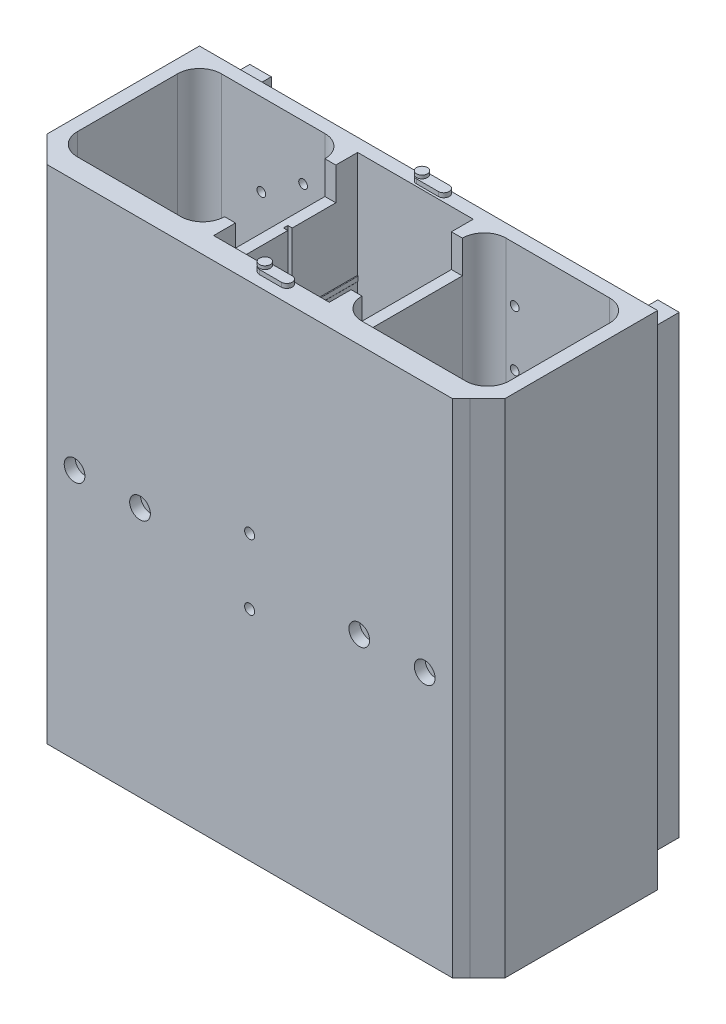
SolidWorks part; units mm, degrees
ref_plane "前视基准面" through (0, 0, 0) normal (0, 0, 1) x (1, 0, 0)
ref_plane "上视基准面" through (0, 0, 0) normal (0, 1, 0) x (1, 0, 0)
ref_plane "右视基准面" through (0, 0, 0) normal (1, 0, 0) x (0, 0, -1)
other "Configuration Table"
sketch "草图1" plane through (0, 0, 0) normal (0, 0, 1) x (1, 0, 0)
  line L1 (0, 0) -> (210, 0)
  line L2 (0, 0) -> (0, 230)
  line L3 (0, 230) -> (210, 230)
  line L4 (210, 0) -> (210, 230)
  line L5 (0, 0) -> (210, 230) construction
  line L6 (0, 230) -> (210, 0) construction
  line L7 (0, 230) -> (26, 230)
  line L8 (0, 230) -> (0, 0)
  line L9 (0, 0) -> (26, 0)
  point P4 (105, 115)
  point P8 (13, 115)
  dimension "D1" = 230
  dimension "D2" = 210
extrude "凸台-拉伸1" add sketch "草图1" along normal blind 6 contours L1 L4 L3 L2
sketch "草图2" plane through (0, 0, 0) normal (0, 0, -1) x (-1, 0, 0)
  line L0 (0, 230) -> (-210, 230) construction
  line L1 (0, 0) -> (-210, 0) construction
  line L2 (-210, 230) -> (-184, 230)
  line L3 (-210, 230) -> (-210, 0)
  line L4 (-210, 0) -> (-184, 0)
  line L5 (-184, 230) -> (-184, 0) construction
  line L6 (-210, 230) -> (-184, 0) construction
  line L7 (-210, 0) -> (-184, 230) construction
  line L9 (0, 230) -> (-20, 230)
  line L10 (0, 230) -> (0, 0)
  line L11 (0, 0) -> (-20, 0)
  line L13 (0, 230) -> (-20, 0) construction
  line L14 (0, 0) -> (-20, 230) construction
  line L15 (-204.925, 219.25) -> (-195.075, 219.25)
  line L16 (-204.925, 219.25) -> (-204.925, 10.75)
  line L17 (-204.925, 10.75) -> (-195.075, 10.75)
  line L18 (-195.075, 219.25) -> (-195.075, 10.75)
  line L19 (-204.925, 219.25) -> (-195.075, 10.75) construction
  line L20 (-204.925, 10.75) -> (-195.075, 219.25) construction
  line L21 (-17.925, 219.25) -> (-8.075, 219.25)
  line L22 (-17.925, 219.25) -> (-17.925, 10.75)
  line L23 (-17.925, 10.75) -> (-8.075, 10.75)
  line L24 (-8.075, 219.25) -> (-8.075, 10.75)
  line L25 (-17.925, 219.25) -> (-8.075, 10.75) construction
  line L26 (-17.925, 10.75) -> (-8.075, 219.25) construction
  point P6 (-197, 115)
  point P18 (-200, 115)
  point P23 (-13, 115)
  dimension "D1" = 26
  dimension "D2" = 20
  dimension "D3" = 208.5
  dimension "D4" = 9.85
  dimension "D5" = 10
  dimension "D6" = 115
  dimension "D7" = 208.5
  dimension "D8" = 115
  dimension "D9" = 13
  dimension "D10" = 9.85
extrude "凸台-拉伸3" add sketch "草图2" along normal blind 15 contours L18 L15 L16 L17 | L24 L21 L22 L23
sketch "草图3" plane through (0, 0, 0) normal (0, 0, -1) x (-1, 0, 0)
  line L0 (0, 0) -> (-210, 0) construction
  line L1 (-210, 230) -> (-184, 230)
  line L2 (-210, 230) -> (-210, 0)
  line L3 (-210, 0) -> (-184, 0)
  line L4 (-184, 230) -> (-184, 0)
  line L5 (-210, 230) -> (-184, 0) construction
  line L6 (-210, 0) -> (-184, 230) construction
  line L7 (-210, 115) -> (119.2636, 115) construction
  line L8 (0, 230) -> (-20, 230)
  line L9 (0, 230) -> (0, 0)
  line L10 (0, 0) -> (-20, 0)
  line L11 (-20, 230) -> (-20, 0)
  line L12 (0, 230) -> (-20, 0) construction
  line L13 (0, 0) -> (-20, 230) construction
  line L14 (-105, 230) -> (-105, 0) construction
  circle A0 centre (-169.6426, 192.25) radius 2
  circle A1 centre (-150.5, 205) radius 2
  circle A2 centre (-150.5, 179.5) radius 2
  circle A3 centre (-150.5, 50.5) radius 2
  circle A4 centre (-150.5, 25) radius 2
  circle A5 centre (-169.6426, 37.75) radius 2
  circle A6 centre (-34.3574, 192.25) radius 2
  circle A7 centre (-53.5, 205) radius 2
  circle A8 centre (-53.5, 179.5) radius 2
  circle A9 centre (-53.5, 50.5) radius 2
  circle A10 centre (-53.5, 25) radius 2
  circle A11 centre (-34.3574, 37.75) radius 2
  point P4 (-197, 115)
  point P12 (-10, 115)
  dimension "D8" = 4
  dimension "D9" = 4
  dimension "D10" = 4
  dimension "D12" = 4
  dimension "D13" = 4
  dimension "D14" = 4
  dimension "D1" = 26
  dimension "D2" = 20
  dimension "D3" = 25.5
  dimension "D4" = 23
  dimension "D5" = 23
  dimension "D6" = 33.5
  dimension "D7" = 33.5
  dimension "D11" = 90
  dimension "D15" = 25.5
  dimension "D16" = 23
  dimension "D17" = 23
  dimension "D18" = 33.5
  dimension "D19" = 33.5
  dimension "D20" = 90
extrude "切除-拉伸1" cut sketch "草图3" against normal blind 10 contours A10 | A11 | A9 | A6 | A8 | A7 | A1 | A2 | A0 | A4 | A3 | A5
chamfer "倒角1" [suppressed] distance 10 angle 45
sketch "草图5" [suppressed] plane through (0, 0, 0) normal (0, 0, -1) x (-1, 0, 0)
  line L0 (-172.5, 115) -> (-135, 115) construction
  line L1 (-10, 230) -> (-200, 230) construction
  line L2 (-210, 10) -> (-210, 220) construction
  line L5 (-210, 220) -> (-210, 0)
  line L8 (-75, 115) -> (-37.5, 115) construction
  line L9 (-210, 0) -> (-184, 220) construction
  line L10 (0, 10) -> (0, 220) construction
  circle A0 centre (-172.5, 115) radius 2.5
  circle A1 centre (-135, 115) radius 2.5
  circle A2 centre (-75, 115) radius 2.5
  circle A3 centre (-37.5, 115) radius 2.5
  point P12 (-197, 110)
  dimension "D3" = 5
  dimension "D4" = 5
  dimension "D8" = 5
  dimension "D9" = 5
  dimension "D1" = 37.5
  dimension "D2" = 115
  dimension "D5" = 75
  dimension "D6" = 26
  dimension "D7" = 37.5
  dimension "D10" = 115
  dimension "D11" = 75
extrude "切除-拉伸2" [suppressed] cut sketch "草图5" against normal blind 10 contours A0 | A1 | A3 | A2
sketch "草图6" plane through (0, 0, 6) normal (0, 0, 1) x (1, 0, 0)
  line L0 (105, 230) -> (105, 0) construction
  line L3 (0, 115) -> (210, 115) construction
  line L6 (86.25, 115) -> (123.75, 115) construction
  line L7 (105, 133.75) -> (105, 96.25) construction
  circle A2 centre (105, 133.75) radius 2.5
  circle A3 centre (105, 96.25) radius 2.5
  point P7 (105, 115)
  point P11 (105, 115)
  dimension "D1" = 37.5
  dimension "D2" = 5
  dimension "D3" = 5
extrude "切除-拉伸3" [suppressed] cut sketch "草图6" against normal blind 10
sketch "草图7" [suppressed] plane through (0, 0, 18) normal (0, 0, 1) x (1, 0, 0)
  line L0 (0, 0) -> (210, 0) construction
  line L1 (0, 230) -> (6, 230)
  line L2 (0, 230) -> (0, 0)
  line L3 (0, 0) -> (6, 0)
  line L4 (6, 230) -> (6, 0)
  line L5 (0, 230) -> (6, 0) construction
  line L6 (0, 0) -> (6, 230) construction
  point P4 (3, 115)
  dimension "D1" = 6
extrude "凸台-拉伸4" [suppressed] add sketch "草图7" along normal blind 55
sketch "草图8" [suppressed] plane through (0, 0, 18) normal (0, 0, 1) x (1, 0, 0)
  line L0 (0, 0) -> (210, 0) construction
  line L1 (210, 230) -> (200.2731, 230)
  line L2 (210, 230) -> (210, 0)
  line L3 (210, 0) -> (200.2731, 0)
  line L4 (200.2731, 230) -> (200.2731, 0)
  line L5 (210, 230) -> (200.2731, 0) construction
  line L6 (210, 0) -> (200.2731, 230) construction
  point P4 (205.1365, 115)
  dimension "D1" = 9.7269
sketch "草图17" plane through (0, 0, 6) normal (0, 0, 1) x (1, 0, 0)
  line L0 (0, 0) -> (210, 0) construction
  line L1 (0, 230) -> (6, 230)
  line L2 (0, 230) -> (0, 0)
  line L3 (0, 0) -> (6, 0)
  line L4 (6, 230) -> (6, 0)
  line L5 (0, 230) -> (6, 0) construction
  line L6 (0, 0) -> (6, 230) construction
  line L8 (210, 230) -> (204, 230)
  line L9 (210, 230) -> (210, 0)
  line L10 (210, 0) -> (204, 0)
  line L11 (204, 230) -> (204, 0)
  line L12 (210, 230) -> (204, 0) construction
  line L13 (210, 0) -> (204, 230) construction
  point P4 (3, 115)
  point P12 (207, 115)
  dimension "D1" = 6
  dimension "D2" = 6
extrude "凸台-拉伸9" add sketch "草图17" along normal blind 66
ref_plane "基准面2" through (0, 0, 72) normal (0, 0, 1) x (1, 0, 0)
sketch "草图18" plane through (0, 0, 72) normal (0, 0, 1) x (1, 0, 0)
  line L0 (210, 230) -> (204, 230) construction
  line L1 (210, 0) -> (210, 230) construction
  line L2 (204, 0) -> (210, 0) construction
  line L3 (6, 0) -> (204, 0) construction
  line L4 (0, 0) -> (6, 0) construction
  line L5 (0, 230) -> (0, 0) construction
  line L6 (6, 230) -> (0, 230) construction
  line L7 (6, 230) -> (204, 230) construction
  line L8 (210, 230) -> (204, 230)
  line L9 (210, 0) -> (210, 230)
  line L10 (204, 0) -> (210, 0)
  line L11 (6, 0) -> (204, 0)
  line L12 (0, 0) -> (6, 0)
  line L13 (0, 230) -> (0, 0)
  line L14 (6, 230) -> (0, 230)
  line L15 (6, 230) -> (204, 230)
extrude "凸台-拉伸10" add sketch "草图18" along normal blind 6
chamfer "倒角3" distance 8 angle 45 2 edges at (0, 115, 78) (210, 115, 78)
sketch "草图19" plane through (0, 0, 72) normal (0, 0, -1) x (-1, 0, 0)
  line L0 (-105, 230) -> (-105, 0) construction
  line L2 (-131.5, 230) -> (-136.5, 230)
  line L3 (0, 230) -> (-210, 230) construction
  line L4 (0, 0) -> (-210, 0) construction
  line L5 (-131.5, 230) -> (-131.5, 0)
  line L6 (-131.5, 230) -> (-78.5, 230)
  line L7 (-131.5, 230) -> (-131.5, 0)
  line L8 (-131.5, 0) -> (-78.5, 0)
  line L9 (-78.5, 230) -> (-78.5, 0)
  line L10 (-131.5, 230) -> (-78.5, 0) construction
  line L11 (-131.5, 0) -> (-78.5, 230) construction
  line L12 (-131.5, 0) -> (-136.5, 0)
  line L13 (-136.5, 230) -> (-136.5, 0)
  line L14 (-131.5, 230) -> (-136.5, 0) construction
  line L15 (-131.5, 0) -> (-136.5, 230) construction
  line L16 (-78.5, 230) -> (-73.5, 230)
  line L17 (-78.5, 230) -> (-78.5, 0)
  line L18 (-78.5, 0) -> (-73.5, 0)
  line L19 (-73.5, 230) -> (-73.5, 0)
  line L20 (-78.5, 230) -> (-73.5, 0) construction
  line L21 (-78.5, 0) -> (-73.5, 230) construction
  point P10 (-105, 115)
  point P13 (-134, 115)
  point P16 (-76, 115)
  dimension "D1" = 53
  dimension "D2" = 0
  dimension "D3" = 5
  dimension "D4" = 5
extrude "凸台-拉伸11" add sketch "草图19" along normal blind 66 contours L19 L7 L9 L4 | L7 L13 L4 L5
fillet "圆角4" radius 10 8 edges at (136.5, 115, 72) (136.5, 115, 6) (204, 115, 6) (204, 115, 72) (73.5, 115, 6) (73.5, 115, 72) (6, 115, 6) (6, 115, 72)
sketch "草图21" plane through (0, 0, 72) normal (0, 0, 1) x (1, 0, 0)
  line L0 (8, 115) -> (202, 115) construction
  line L1 (8, 230) -> (8, 0) construction
  line L2 (202, 0) -> (202, 230) construction
  line L3 (105, 230) -> (105, 0) construction
  line L4 (202, 230) -> (8, 230) construction
  line L5 (8, 0) -> (202, 0) construction
  line L6 (105, 130) -> (105, 100) construction
  circle A0 centre (105, 130) radius 2.3
  circle A1 centre (105, 100) radius 2.3
  point P14 (105, 115)
  dimension "D3" = 4.6
  dimension "D4" = 4.6
  dimension "D1" = 0
  dimension "D2" = 30
extrude "切除-拉伸9" cut sketch "草图21" along normal blind 6 contours A1 | A0
sketch "草图23" plane through (78.5, 0, 0) normal (1, 0, 0) x (0, 0, -1)
  line L0 (-6, 80) -> (-70, 80)
  line L1 (-6, 230) -> (-70, 230) construction
  line L2 (-6, 230) -> (-6, 0) construction
  line L3 (-6, 0) -> (-70, 0) construction
  line L4 (-70, 230) -> (-70, 0) construction
  line L5 (-6, 230) -> (-70, 0) construction
  line L6 (-6, 0) -> (-70, 230) construction
  line L7 (-6, 230) -> (-70, 230)
  line L8 (-6, 230) -> (-6, 40)
  line L9 (-6, 40) -> (-70, 40)
  line L10 (-70, 230) -> (-70, 40)
  line L11 (-6, 230) -> (-70, 40) construction
  line L12 (-6, 40) -> (-70, 230) construction
  point P4 (-38, 115)
  point P9 (-38, 135)
  dimension "D1" = 190
  dimension "D2" = 40
sketch "草图24" plane through (0, 0, 6) normal (0, 0, 1) x (1, 0, 0)
  line L0 (78.5, 80.5) -> (78.5, 79.5) construction
  line L1 (78.5, 230) -> (78.5, 40) construction
  line L2 (80, 80.5) -> (80, 79.5)
  line L4 (78.5, 82) -> (78.5, 78)
  arc A0 (80, 80.5) -> (78.5, 82) centre (78.5, 80.5) ccw
  arc A1 (78.5, 78) -> (80, 79.5) centre (78.5, 79.5) ccw
  point P0 (78.5, 80)
  point P6 (78.5, 80)
  dimension "D3" = 1.5
  dimension "D4" = 1.5
  dimension "D1" = 0
  dimension "D2" = 1
extrude "凸台-拉伸12" [suppressed] add sketch "草图24" along normal blind 66
ref_plane "基准面3" through (105, 0, 0) normal (-1, 0, 0) x (0, 0, 1)
mirror "镜向1" [suppressed] about plane through (105, 0, 0) normal (-1, 0, 0)
sketch "草图25" plane through (0, 0, 72) normal (0, 0, -1) x (-1, 0, 0)
  line L8 (-131.5, 230) -> (-131.5, 0)
  line L11 (-131.5, 0) -> (-78.5, 0)
  line L12 (-78.5, 0) -> (-78.5, 230)
  line L15 (-78.5, 230) -> (-131.5, 230)
  line L16 (-131.5, 230) -> (-131.5, 0)
  line L19 (-131.5, 0) -> (-78.5, 0)
  line L20 (-78.5, 0) -> (-78.5, 230)
  line L23 (-78.5, 230) -> (-131.5, 230)
  dimension "D1" = 0
sketch "草图26" plane through (0, 0, 72) normal (0, 0, -1) x (-1, 0, 0)
  line L0 (-131.5, 181) -> (-131.5, 179) construction
  line L1 (-131.5, 230) -> (-131.5, 0) construction
  line L2 (-131.26, 181) -> (-131.26, 179)
  line L3 (-131.74, 181) -> (-131.74, 179)
  line L4 (-78.5, 230) -> (-131.5, 230) construction
  line L5 (-131.5, 230) -> (-131.5, 0) construction
  line L6 (-78.5, 230) -> (-131.5, 230) construction
  line L7 (-131.5, 22.5) -> (-131.5, 20.5) construction
  line L8 (-131.26, 22.5) -> (-131.26, 20.5)
  line L9 (-131.74, 22.5) -> (-131.74, 20.5)
  arc A0 (-131.26, 181) -> (-131.74, 181) centre (-131.5, 181) ccw
  arc A1 (-131.74, 179) -> (-131.26, 179) centre (-131.5, 179) ccw
  arc A2 (-131.26, 22.5) -> (-131.74, 22.5) centre (-131.5, 22.5) ccw
  arc A3 (-131.74, 20.5) -> (-131.26, 20.5) centre (-131.5, 20.5) ccw
  point P4 (-131.5, 180)
  point P14 (-131.5, 21.5)
  dimension "D1" = 0.24
  dimension "D2" = 2
  dimension "D3" = 50
  dimension "D4" = 2
extrude "凸台-拉伸13" add sketch "草图26" along normal blind 66
mirror "镜向2" about plane through (105, 0, 0) normal (-1, 0, 0) of "凸台-拉伸13"
sketch "草图28" plane through (0, 0, 72) normal (0, 0, -1) x (-1, 0, 0)
  line L0 (-78.5, 230) -> (-131.5, 230) construction
  line L1 (-78.5, 230) -> (-131.5, 230) construction
  line L2 (-131.5, 230) -> (-131.5, 0) construction
  line L3 (-131.5, 11.46) -> (-78.5, 11.46)
  line L4 (-131.5, 11.46) -> (-131.5, 8.46)
  line L5 (-131.5, 8.46) -> (-78.5, 8.46)
  line L6 (-78.5, 11.46) -> (-78.5, 8.46)
  line L7 (-131.5, 11.46) -> (-78.5, 8.46) construction
  line L8 (-131.5, 8.46) -> (-78.5, 11.46) construction
  line L9 (-78.5, 230) -> (-78.5, 0) construction
  point P6 (-105, 9.96)
  point P11 (-78.5, 20.2624)
  dimension "D1" = 218.54
  dimension "D2" = 3
extrude "凸台-拉伸14" add sketch "草图28" along normal blind 66
sketch "草图30" plane through (0, 230, 0) normal (0, 1, 0) x (1, 0, 0)
  line L0 (78.5, -6) -> (131.5, -6) construction
  line L1 (78.5, -6) -> (131.5, -6) construction
  line L2 (78.5, -6) -> (78.5, -70) construction
  line L3 (78.5, -36) -> (76.5, -36)
  line L4 (78.5, -36) -> (78.5, -38)
  line L5 (78.5, -38) -> (76.5, -38)
  line L6 (76.5, -36) -> (76.5, -38)
  line L7 (78.5, -36) -> (76.5, -38) construction
  line L8 (78.5, -38) -> (76.5, -36) construction
  point P6 (77.5, -37)
  dimension "D1" = 2
  dimension "D2" = 30
  dimension "D3" = 2
extrude "切除-拉伸10" cut sketch "草图30" against normal blind 35
sketch "草图31" plane through (0, 8.46, 0) normal (0, -1, 0) x (1, 0, 0)
  line L0 (105, 72) -> (105, 6) construction
  line L1 (105, 16.2) -> (117.5, 16.2) construction
  line L2 (98, 23.2) -> (112, 23.2)
  line L3 (98, 23.2) -> (98, 9.2)
  line L4 (131.5, 72) -> (78.5, 72)
  line L5 (78.5, 72) -> (78.5, 6)
  line L6 (78.5, 6) -> (131.5, 6)
  line L7 (131.5, 6) -> (131.5, 72)
  line L8 (131.5, 72) -> (78.5, 72) construction
  line L9 (78.5, 72) -> (78.5, 6) construction
  line L10 (78.5, 6) -> (131.5, 6) construction
  line L11 (131.5, 6) -> (131.5, 72) construction
  line L12 (98, 9.2) -> (112, 9.2)
  line L13 (112, 23.2) -> (112, 9.2)
  line L14 (98, 23.2) -> (112, 9.2) construction
  line L15 (98, 9.2) -> (112, 23.2) construction
  circle A0 centre (92.7, 16.2) radius 1.35
  circle A1 centre (117.3, 16.2) radius 1.35
  point P10 (105, 16.2)
  dimension "D8" = 2.7
  dimension "D9" = 2.7
  dimension "D2" = 14
  dimension "D3" = 14
  dimension "D4" = 12.3
  dimension "D5" = 12.3
  dimension "D6" = 3.2
  dimension "D7" = 0
  dimension "D1" = 0
extrude "切除-拉伸11" cut sketch "草图31" against normal through all
sketch "草图32" plane through (0, 0, 6) normal (0, 0, 1) x (1, 0, 0)
  line L0 (131.5, 8.46) -> (78.5, 8.46) construction
  line L1 (119.5, 8.46) -> (131.5, 8.46)
  line L2 (119.5, 8.46) -> (119.5, -1.54)
  line L3 (119.5, -1.54) -> (131.5, -1.54)
  line L4 (131.5, 8.46) -> (131.5, -1.54)
  line L5 (119.5, 8.46) -> (131.5, -1.54) construction
  line L6 (119.5, -1.54) -> (131.5, 8.46) construction
  line L7 (131.5, 8.46) -> (78.5, 8.46) construction
  line L8 (131.5, 8.46) -> (131.5, 0) construction
  line L9 (131.5, 8.46) -> (131.5, 0) construction
  line L10 (78.5, 0) -> (131.5, 0) construction
  line L11 (78.5, 0) -> (131.5, 0) construction
  point P4 (125.5, 3.46)
  dimension "D1" = 10
  dimension "D2" = 0
  dimension "D3" = 0
  dimension "D4" = 12
extrude "切除-拉伸12" [suppressed] cut sketch "草图32" against normal through all
sketch "草图33" [suppressed] plane through (131.5, 0, 0) normal (-1, 0, 0) x (0, 0, 1)
  line L0 (0, 8.46) -> (72, 8.46) construction
  line L1 (30, 8.46) -> (50, 8.46)
  line L2 (30, 8.46) -> (30, 0)
  line L3 (30, 0) -> (50, 0)
  line L4 (50, 8.46) -> (50, 0)
  line L5 (30, 8.46) -> (50, 0) construction
  line L6 (30, 0) -> (50, 8.46) construction
  line L7 (0, 0) -> (72, 0) construction
  line L8 (0, 0) -> (0, 8.46) construction
  point P4 (40, 4.23)
  point P9 (30, 4.23)
  dimension "D1" = 20
  dimension "D2" = 30
extrude "切除-拉伸13" [suppressed] cut sketch "草图33" against normal up to next
sketch "草图34" plane through (0, 0, 72) normal (0, 0, -1) x (-1, 0, 0)
  line L0 (-170.25, 230) -> (-170.25, 0) construction
  line L1 (-194, 115) -> (-146.5, 115) construction
  line L2 (-185.25, 115) -> (-155.25, 115)
  line L4 (-194, 0) -> (-146.5, 0)
  line L19 (-194, 0) -> (-146.5, 0)
  line L23 (-146.5, 0) -> (-146.5, 230)
  line L25 (-146.5, 0) -> (-146.5, 230)
  line L27 (-146.5, 230) -> (-194, 230)
  line L28 (-146.5, 230) -> (-194, 230)
  line L29 (-194, 230) -> (-194, 0)
  line L30 (-194, 230) -> (-194, 0)
  circle A0 centre (-185.25, 115) radius 2.25
  circle A1 centre (-155.25, 115) radius 2.25
  point P12 (-170.25, 115)
  dimension "D2" = 4.5
  dimension "D3" = 4.5
  dimension "D4" = 30
  dimension "D1" = 0
extrude "切除-拉伸14" cut sketch "草图34" against normal blind 30 contours A0 | A1
sketch "草图36" plane through (0, 0, 72) normal (0, 0, -1) x (-1, 0, 0)
  line L0 (-39.75, 230) -> (-39.75, 0) construction
  line L1 (-63.5, 115) -> (-16, 115) construction
  line L2 (-54.75, 115) -> (-24.75, 115)
  line L4 (-16, 230) -> (-63.5, 230)
  line L19 (-16, 230) -> (-63.5, 230)
  line L23 (-63.5, 230) -> (-63.5, 0)
  line L25 (-63.5, 230) -> (-63.5, 0)
  line L27 (-63.5, 0) -> (-16, 0)
  line L28 (-63.5, 0) -> (-16, 0)
  line L29 (-16, 0) -> (-16, 230)
  line L30 (-16, 0) -> (-16, 230)
  circle A0 centre (-54.75, 115) radius 2.25
  circle A1 centre (-24.75, 115) radius 2.25
  point P12 (-39.75, 115)
  dimension "D2" = 4.5
  dimension "D3" = 4.5
  dimension "D4" = 30
  dimension "D1" = 0
extrude "切除-拉伸15" cut sketch "草图36" against normal blind 30
sketch "草图37" plane through (0, 0, 72) normal (0, 0, -1) x (-1, 0, 0)
  line L12 (-131.5, 11.46) -> (-78.5, 11.46)
  line L13 (-78.5, 11.46) -> (-78.5, 20.26)
  line L14 (-78.74, 20.5) -> (-78.74, 22.5)
  line L15 (-78.5, 22.74) -> (-78.5, 178.76)
  line L16 (-78.74, 179) -> (-78.74, 181)
  line L17 (-78.5, 181.24) -> (-78.5, 230)
  line L18 (-78.5, 230) -> (-131.5, 230)
  line L19 (-131.5, 230) -> (-131.5, 181.24)
  line L20 (-131.26, 181) -> (-131.26, 179)
  line L21 (-131.5, 178.76) -> (-131.5, 22.74)
  line L22 (-131.26, 22.5) -> (-131.26, 20.5)
  line L23 (-131.5, 20.26) -> (-131.5, 11.46)
  line L25 (-78.5, 11.46) -> (-78.5, 20.26)
  line L26 (-78.74, 20.5) -> (-78.74, 22.5)
  line L27 (-78.5, 22.74) -> (-78.5, 178.76)
  line L28 (-78.74, 179) -> (-78.74, 181)
  line L29 (-78.5, 181.24) -> (-78.5, 230)
  line L30 (-78.5, 230) -> (-131.5, 230)
  line L31 (-131.5, 230) -> (-131.5, 181.24)
  line L32 (-131.26, 181) -> (-131.26, 179)
  line L33 (-131.5, 178.76) -> (-131.5, 22.74)
  line L34 (-131.26, 22.5) -> (-131.26, 20.5)
  line L35 (-131.5, 20.26) -> (-131.5, 11.46)
  line L41 (-131.5, 11.46) -> (-78.5, 11.46)
  circle A1 centre (-105, 130) radius 2.3
  circle A2 centre (-105, 130) radius 2.3
  circle A3 centre (-105, 100) radius 2.3
  circle A4 centre (-105, 100) radius 2.3
  arc A8 (-78.74, 20.5) -> (-78.5, 20.26) centre (-78.5, 20.5) ccw
  arc A9 (-78.5, 22.74) -> (-78.74, 22.5) centre (-78.5, 22.5) ccw
  arc A10 (-78.74, 179) -> (-78.5, 178.76) centre (-78.5, 179) ccw
  arc A11 (-78.5, 181.24) -> (-78.74, 181) centre (-78.5, 181) ccw
  arc A12 (-131.26, 181) -> (-131.5, 181.24) centre (-131.5, 181) ccw
  arc A13 (-131.5, 178.76) -> (-131.26, 179) centre (-131.5, 179) ccw
  arc A14 (-131.26, 22.5) -> (-131.5, 22.74) centre (-131.5, 22.5) ccw
  arc A15 (-131.5, 20.26) -> (-131.26, 20.5) centre (-131.5, 20.5) ccw
  arc A16 (-78.74, 20.5) -> (-78.5, 20.26) centre (-78.5, 20.5) ccw
  arc A17 (-78.5, 22.74) -> (-78.74, 22.5) centre (-78.5, 22.5) ccw
  arc A18 (-78.74, 179) -> (-78.5, 178.76) centre (-78.5, 179) ccw
  arc A19 (-78.5, 181.24) -> (-78.74, 181) centre (-78.5, 181) ccw
  arc A20 (-131.26, 181) -> (-131.5, 181.24) centre (-131.5, 181) ccw
  arc A21 (-131.5, 178.76) -> (-131.26, 179) centre (-131.5, 179) ccw
  arc A22 (-131.26, 22.5) -> (-131.5, 22.74) centre (-131.5, 22.5) ccw
  arc A23 (-131.5, 20.26) -> (-131.26, 20.5) centre (-131.5, 20.5) ccw
  dimension "D1" = 0
  dimension "D2" = 0
  dimension "D3" = 0
extrude "凸台-拉伸15" [suppressed] add sketch "草图37" along normal blind 4
sketch "草图39" plane through (73.5, 0, 0) normal (-1, 0, 0) x (0, 0, 1)
  line L1 (16, 230) -> (62, 230)
  line L2 (16, 230) -> (16, 215)
  line L3 (16, 215) -> (62, 215)
  line L4 (62, 230) -> (16, 230)
  line L5 (16, 230) -> (16, 0)
  line L6 (16, 0) -> (62, 0)
  line L7 (16, 230) -> (16, 0)
  line L8 (62, 230) -> (16, 230)
  line L10 (16, 0) -> (62, 0)
  line L12 (62, 230) -> (62, 215)
  line L13 (16, 230) -> (62, 215) construction
  line L14 (16, 215) -> (62, 230) construction
  line L18 (62, 0) -> (62, 230)
  line L19 (62, 0) -> (62, 230)
  point P6 (39, 222.5)
  line M6 (62, 230) -> (16, 230)
  line M7 (16, 230) -> (16, 0)
  line M9 (62, 0) -> (62, 230)
  dimension "D2" = 15
  dimension "D1" = 0
extrude "切除-拉伸16" cut sketch "草图39" against normal blind 104 contours L3 M7 M9 M6
sketch "草图40" plane through (0, 230, 0) normal (0, 1, 0) x (1, 0, 0)
  line L0 (105, 0) -> (105, -6) construction
  line L1 (0, 0) -> (210, 0) construction
  line L2 (78.5, -6) -> (131.5, -6) construction
  circle A0 centre (105, -3) radius 1.5
  dimension "D1" = 3
extrude "凸台-拉伸16" add sketch "草图40" along normal blind 3
sketch "草图41" plane through (0, 233, 0) normal (0, 1, 0) x (1, 0, 0)
  circle A0 centre (105, -3) radius 2.5
  dimension "D1" = 5
extrude "凸台-拉伸17" add sketch "草图41" along normal blind 1.5
sketch "草图42" plane through (0, 230, 0) normal (0, 1, 0) x (1, 0, 0)
  line L6 (0, 0) -> (0, -70)
  line L7 (0, -70) -> (8, -78)
  line L8 (8, -78) -> (202, -78)
  line L9 (202, -78) -> (210, -70)
  line L10 (210, -70) -> (210, 0)
  line L11 (210, 0) -> (0, 0)
  line L12 (0, 0) -> (0, -70)
  line L13 (0, -70) -> (8, -78)
  line L14 (8, -78) -> (202, -78)
  line L15 (202, -78) -> (210, -70)
  line L16 (210, -70) -> (210, 0)
  line L17 (210, 0) -> (0, 0)
  circle A0 centre (105, -3) radius 1.6
  circle A1 centre (105, -3) radius 1.5
  circle A2 centre (105, -3) radius 1.5 construction
  dimension "D3" = 3.2
  dimension "D1" = 0
  dimension "D2" = 0
ref_plane "基准面4" through (0, 230.5, 0) normal (0, 1, 0) x (1, 0, 0)
sketch "草图44" plane through (0, 230.5, 0) normal (0, 1, 0) x (1, 0, 0)
  line L0 (105, -3) -> (115, -3) construction
  line L1 (105, -0.5) -> (115, -0.5)
  line L2 (105, -5.5) -> (115, -5.5)
  arc A2 (105, -0.5) -> (105, -5.5) centre (105, -3) ccw
  arc A3 (115, -5.5) -> (115, -0.5) centre (115, -3) ccw
  circle A4 centre (105, -3) radius 1.62
  point P3 (110, -3)
  dimension "D1" = 2.5
  dimension "D2" = 10
  dimension "D3" = 3.24
extrude "凸台-拉伸19" add sketch "草图44" along normal blind 2 separate body
ref_plane "基准面5" through (0, 0, 39) normal (0, 0, 1) x (1, 0, 0)
mirror "镜向3" about plane through (0, 0, 39) normal (0, 0, 1) of "凸台-拉伸16", "凸台-拉伸17", "凸台-拉伸19"
sketch "草图45" plane through (0, 230, 0) normal (0, 1, 0) x (1, 0, 0)
  line L0 (105, -75) -> (115, -75) construction
  line L1 (105, -72.5) -> (115, -72.5)
  line L2 (105, -77.5) -> (115, -77.5)
  circle A0 centre (105, -75) radius 1.62
  arc A1 (105, -72.5) -> (105, -77.5) centre (105, -75) ccw
  arc A2 (115, -77.5) -> (115, -72.5) centre (115, -75) ccw
  point P3 (110, -75)
  dimension "D1" = 3.24
  dimension "D2" = 2.5
  dimension "D3" = 10
sketch "草图46" plane through (0, 230.5, 0) normal (0, 1, 0) x (1, 0, 0)
  line L2 (115, -72.5) -> (105, -72.5)
  line L3 (105, -77.5) -> (115, -77.5)
  line L4 (115, -72.5) -> (105, -72.5)
  line L5 (105, -77.5) -> (115, -77.5)
  circle A1 centre (105, -75) radius 1.62
  circle A3 centre (105, -75) radius 1.62
  arc A4 (115, -77.5) -> (115, -72.5) centre (115, -75) ccw
  arc A5 (105, -72.5) -> (105, -77.5) centre (105, -75) ccw
  arc A6 (115, -77.5) -> (115, -72.5) centre (115, -75) ccw
  arc A7 (105, -72.5) -> (105, -77.5) centre (105, -75) ccw
  dimension "D1" = 0
  dimension "D2" = 0
extrude "凸台-拉伸20" add sketch "草图46" along normal blind 2 separate body
sketch "草图49" plane through (0, 0, 6) normal (0, 0, 1) x (1, 0, 0)
  line L1 (78.5, 0) -> (90.5, 0)
  line L2 (78.5, 0) -> (78.5, 8.46)
  line L3 (78.5, 8.46) -> (90.5, 8.46)
  line L4 (131.5, 0) -> (131.5, 8.46)
  line L5 (131.5, 8.46) -> (78.5, 8.46)
  line L6 (78.5, 8.46) -> (78.5, 0)
  line L7 (78.5, 0) -> (131.5, 0)
  line L8 (131.5, 0) -> (131.5, 8.46)
  line L9 (131.5, 8.46) -> (78.5, 8.46)
  line L10 (78.5, 8.46) -> (78.5, 0)
  line L11 (78.5, 0) -> (131.5, 0)
  line L12 (90.5, 0) -> (90.5, 8.46)
  line L13 (78.5, 0) -> (90.5, 8.46) construction
  line L14 (78.5, 8.46) -> (90.5, 0) construction
  point P6 (84.5, 4.23)
  line M7 (131.5, 8.46) -> (78.5, 8.46)
  line M8 (78.5, 8.46) -> (78.5, 0)
  line M9 (78.5, 0) -> (131.5, 0)
  dimension "D2" = 12
  dimension "D1" = 0
extrude "切除-拉伸17" cut sketch "草图49" against normal blind 10 contours L12 M9 M7 M8
sketch "草图50" plane through (78.5, 0, 0) normal (1, 0, 0) x (0, 0, -1)
  line L1 (-30, 8.46) -> (-50, 8.46)
  line L2 (-30, 8.46) -> (-30, 0)
  line L3 (-30, 0) -> (-50, 0)
  line L4 (0, 8.46) -> (-72, 8.46)
  line L5 (-72, 8.46) -> (-72, 0)
  line L6 (-72, 0) -> (0, 0)
  line L7 (0, 0) -> (0, 8.46)
  line L8 (0, 8.46) -> (-72, 8.46)
  line L9 (-72, 8.46) -> (-72, 0)
  line L10 (-72, 0) -> (0, 0)
  line L11 (0, 0) -> (0, 8.46)
  line L12 (-50, 8.46) -> (-50, 0)
  line L13 (-30, 8.46) -> (-50, 0) construction
  line L14 (-30, 0) -> (-50, 8.46) construction
  point P8 (-40, 4.23)
  line M7 (0, 8.46) -> (-72, 8.46)
  line M9 (-72, 0) -> (0, 0)
  dimension "D2" = 30
  dimension "D3" = 20
  dimension "D1" = 0
extrude "切除-拉伸18" cut sketch "草图50" against normal blind 10 contours L12 L2 M7 M9
sketch "草图51" plane through (0, 0, 78) normal (0, 0, 1) x (1, 0, 0)
  line L4 (202, 230) -> (8, 230)
  line L5 (8, 230) -> (8, 0)
  line L6 (8, 0) -> (202, 0)
  line L7 (202, 0) -> (202, 230)
  line L8 (202, 230) -> (8, 230)
  line L9 (8, 230) -> (8, 0)
  line L10 (8, 0) -> (202, 0)
  line L11 (202, 0) -> (202, 230)
  dimension "D1" = 0
extrude "凸台-拉伸22" add sketch "草图51" along normal blind 4
chamfer "倒角6" distance 4 angle 45 2 edges at (202, 115, 82) (8, 115, 82)
sketch "草图54" plane through (0, 0, 82) normal (0, 0, 1) x (1, 0, 0)
  line L4 (16, 0) -> (63.5, 0)
  line L5 (63.5, 0) -> (63.5, 230)
  line L6 (63.5, 230) -> (16, 230)
  line L7 (16, 230) -> (16, 0)
  line L8 (16, 0) -> (63.5, 0)
  line L9 (63.5, 0) -> (63.5, 230)
  line L10 (63.5, 230) -> (16, 230)
  line L11 (16, 230) -> (16, 0) construction
  line L12 (194, 230) -> (146.5, 230)
  line L13 (146.5, 230) -> (146.5, 0)
  line L14 (146.5, 0) -> (194, 0)
  line L15 (194, 0) -> (194, 230)
  line L16 (194, 230) -> (146.5, 230)
  line L17 (146.5, 230) -> (146.5, 0) construction
  line L18 (146.5, 0) -> (194, 0)
  line L19 (194, 0) -> (194, 230)
  circle A0 centre (24.75, 115) radius 4.75
  circle A1 centre (24.75, 115) radius 2.25
  circle A2 centre (24.75, 115) radius 2.25 construction
  circle A3 centre (54.75, 115) radius 2.25
  circle A4 centre (54.75, 115) radius 2.25 construction
  circle A5 centre (155.25, 115) radius 2.25
  circle A6 centre (155.25, 115) radius 2.25 construction
  circle A7 centre (185.25, 115) radius 2.25
  circle A8 centre (185.25, 115) radius 2.25 construction
  circle A9 centre (105, 130) radius 2.3
  circle A10 centre (105, 130) radius 2.3 construction
  circle A11 centre (105, 100) radius 2.3
  circle A12 centre (105, 100) radius 2.3 construction
  circle A13 centre (54.75, 115) radius 4.75
  circle A16 centre (155.25, 115) radius 4.75
  circle A17 centre (185.25, 115) radius 4.75
  circle A18 centre (105, 130) radius 2.3
  circle A19 centre (105, 100) radius 2.3
  dimension "D9" = 9.5
  dimension "D10" = 9.5
  dimension "D13" = 9.5
  dimension "D14" = 9.5
  dimension "D1" = 0
  dimension "D2" = 0
  dimension "D3" = 0
  dimension "D4" = 0
  dimension "D5" = 0
  dimension "D6" = 0
  dimension "D7" = 0
  dimension "D8" = 0
extrude "切除-拉伸21" cut sketch "草图54" against normal blind 5 contours A13 | A18 | A19 | A0 | A16 | A17
